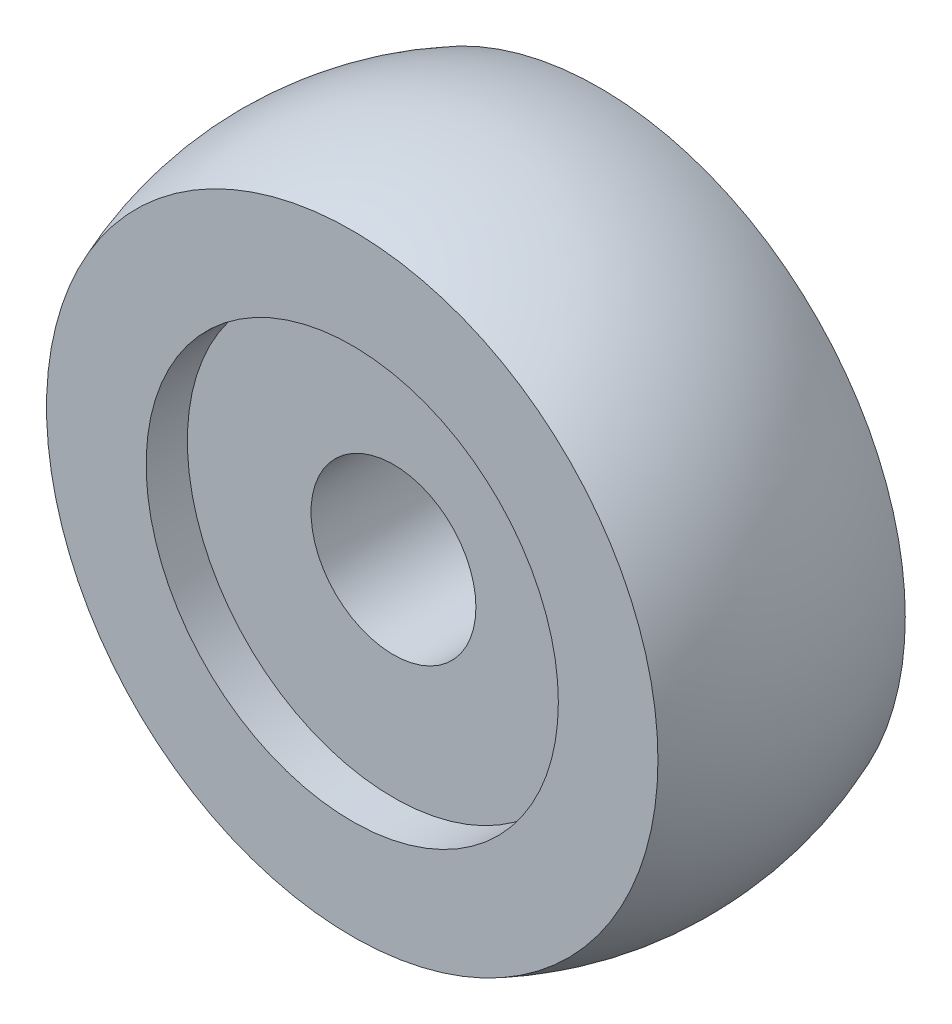
SolidWorks part; units mm, degrees
ref_plane "前视基准面" through (0, 0, 0) normal (0, 0, 1) x (1, 0, 0)
ref_plane "上视基准面" through (0, 0, 0) normal (0, 1, 0) x (1, 0, 0)
ref_plane "右视基准面" through (0, 0, 0) normal (1, 0, 0) x (0, 0, -1)
sketch "草图1" plane through (0, 0, 0) normal (0, 0, 1) x (1, 0, 0)
  line L0 (0, 8) -> (0, -8) construction
  circle A2 centre (0, 0) radius 8
  dimension "D1" = 16
revolve "旋转3" add sketch "草图1" angle 360 about L0 region at (-3.3953, 0, 0)
sketch "草图2" plane through (0, 0, 0) normal (0, 0, 1) x (1, 0, 0)
  circle A0 centre (0, 0) radius 9.0587
extrude "切除-拉伸1" cut sketch "草图2" along normal blind 10 from offset 3
extrude "切除-拉伸2" cut sketch "草图2<2>" against normal blind 10 from offset 3 offset against normal yes
sketch "草图2<2>" plane through (0, 0, 0) normal (0, 0, 1) x (1, 0, 0) same geometry as "草图2"
sketch "草图3" plane through (0, 0, 3) normal (0, 0, 1) x (1, 0, 0)
  circle A0 centre (0, 0) radius 5
  dimension "D1" = 10
extrude "切除-拉伸3" cut sketch "草图3" against normal blind 1
mirror "镜向1" about plane through (0, 0, 0) normal (0, 0, 1) of "切除-拉伸3"
sketch "草图4" plane through (0, 0, 2) normal (0, 0, 1) x (1, 0, 0)
  circle A0 centre (0, 0) radius 2
  dimension "D1" = 4
extrude "切除-拉伸4" cut sketch "草图4" against normal blind 5
